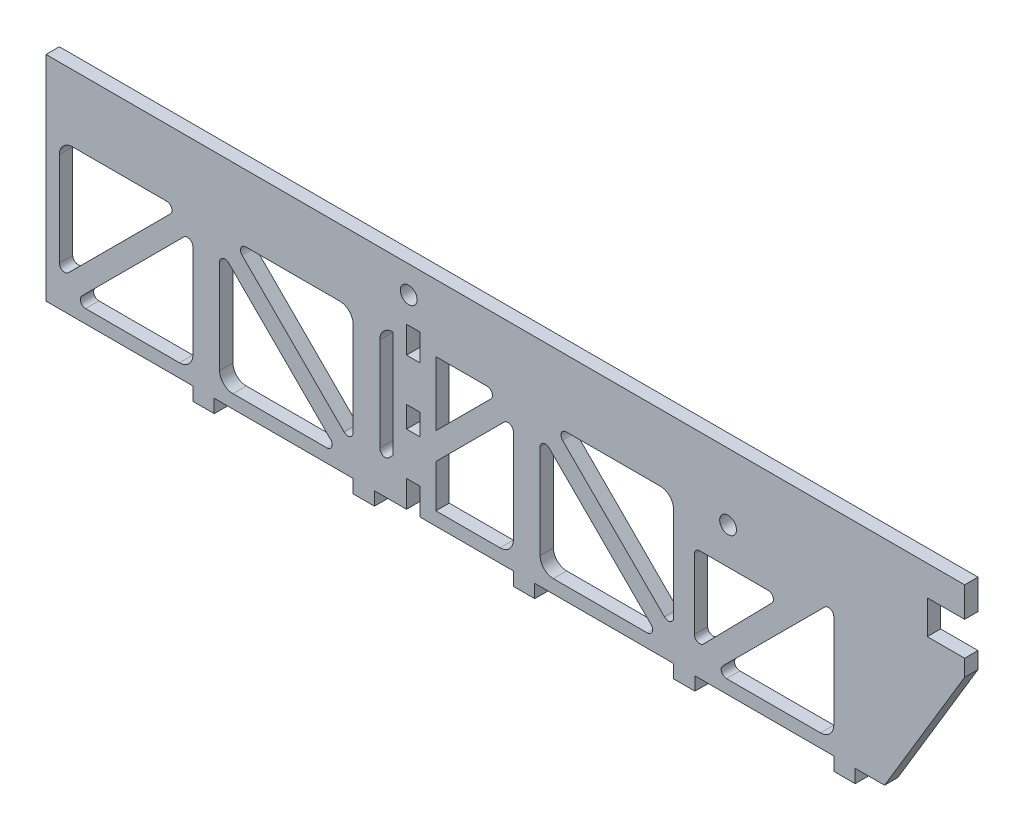
SolidWorks part; units mm, degrees
material "Pine"
ref_plane "Front Plane" through (0, 0, 0) normal (0, 0, 1) x (1, 0, 0)
ref_plane "Top Plane" through (0, 0, 0) normal (0, 1, 0) x (1, 0, 0)
ref_plane "Right Plane" through (0, 0, 0) normal (1, 0, 0) x (0, 0, -1)
sketch "Model" plane through (0, 0, 0) normal (0, 0, 1) x (1, 0, 0)
  line L0 (312.6855, 15.1239) -> (345.2281, 48.2988)
  line L1 (343.4149, 52.6175) -> (310.8722, 52.6175)
  line L2 (308.3322, 50.0775) -> (308.3322, 16.9026)
  line L8 (171.2321, 6.35) -> (215.9, 6.35)
  line L9 (217.9139, 59.1639) -> (169.4361, 10.6861)
  line L10 (222.25, 57.3679) -> (222.25, 12.7)
  line L11 (234.95, 57.3679) -> (234.95, 12.7)
  line L12 (239.2861, 59.1639) -> (287.7639, 10.6861)
  line L13 (241.3, 6.35) -> (285.9679, 6.35)
  line L14 (294.1139, 17.0361) -> (245.6361, 65.5139)
  line L15 (247.4321, 69.85) -> (292.1, 69.85)
  line L16 (298.45, 63.5) -> (298.45, 18.8321)
  line L17 (323.6321, 6.35) -> (368.3, 6.35)
  line L18 (370.3139, 59.1639) -> (321.8361, 10.6861)
  line L19 (374.65, 57.3679) -> (374.65, 12.7)
  line L20 (18.8321, 6.35) -> (63.5, 6.35)
  line L21 (17.0361, 10.6861) -> (65.5139, 59.1639)
  line L22 (69.85, 57.3679) -> (69.85, 12.7)
  line L23 (82.55, 57.3679) -> (82.55, 12.7)
  line L24 (86.8861, 59.1639) -> (135.3639, 10.6861)
  line L25 (88.9, 6.35) -> (133.5679, 6.35)
  line L26 (93.2361, 65.5139) -> (141.7139, 17.0361)
  line L27 (95.0321, 69.85) -> (139.7, 69.85)
  line L28 (146.05, 63.5) -> (146.05, 18.8321)
  line L29 (163.0861, 17.0361) -> (211.5639, 65.5139)
  line L30 (158.75, 63.5) -> (158.75, 18.8321)
  line L31 (165.1, 69.85) -> (209.7679, 69.85)
  line L35 (419.1, 87.376) -> (419.1, 71.374)
  line L36 (436.88, 87.376) -> (419.1, 87.376)
  line L37 (436.88, 87.376) -> (436.88, 95.25)
  line L38 (0, 95.25) -> (436.88, 95.25)
  line L39 (0, 0) -> (0, 95.25)
  line L40 (0, 0) -> (398.78, 0)
  line L41 (436.88, 63.5) -> (398.78, 0)
  line L42 (436.88, 63.5) -> (436.88, 71.374)
  line L43 (419.1, 71.374) -> (436.88, 71.374)
  line L44 (6.35, 63.5) -> (6.35, 18.8321)
  line L45 (12.7, 69.85) -> (57.3679, 69.85)
  line L46 (59.1639, 65.5139) -> (10.6861, 17.0361)
  arc A0 (215.9, 6.35) -> (222.25, 12.7) centre (215.9, 12.7) ccw
  arc A1 (169.4361, 10.6861) -> (171.2321, 6.35) centre (171.2321, 8.89) ccw
  arc A2 (222.25, 57.3679) -> (217.9139, 59.1639) centre (219.71, 57.3679) ccw
  arc A3 (239.2861, 59.1639) -> (234.95, 57.3679) centre (237.49, 57.3679) ccw
  arc A4 (285.9679, 6.35) -> (287.7639, 10.6861) centre (285.9679, 8.89) ccw
  arc A5 (234.95, 12.7) -> (241.3, 6.35) centre (241.3, 12.7) ccw
  arc A6 (247.4321, 69.85) -> (245.6361, 65.5139) centre (247.4321, 67.31) ccw
  arc A7 (298.45, 63.5) -> (292.1, 69.85) centre (292.1, 63.5) ccw
  arc A8 (294.1139, 17.0361) -> (298.45, 18.8321) centre (295.91, 18.8321) ccw
  arc A9 (321.8361, 10.6861) -> (323.6321, 6.35) centre (323.6321, 8.89) ccw
  arc A10 (374.65, 57.3679) -> (370.3139, 59.1639) centre (372.11, 57.3679) ccw
  arc A11 (368.3, 6.35) -> (374.65, 12.7) centre (368.3, 12.7) ccw
  arc A12 (63.5, 6.35) -> (69.85, 12.7) centre (63.5, 12.7) ccw
  arc A13 (17.0361, 10.6861) -> (18.8321, 6.35) centre (18.8321, 8.89) ccw
  arc A14 (69.85, 57.3679) -> (65.5139, 59.1639) centre (67.31, 57.3679) ccw
  arc A15 (86.8861, 59.1639) -> (82.55, 57.3679) centre (85.09, 57.3679) ccw
  arc A16 (133.5679, 6.35) -> (135.3639, 10.6861) centre (133.5679, 8.89) ccw
  arc A17 (82.55, 12.7) -> (88.9, 6.35) centre (88.9, 12.7) ccw
  arc A18 (95.0321, 69.85) -> (93.2361, 65.5139) centre (95.0321, 67.31) ccw
  arc A19 (146.05, 63.5) -> (139.7, 69.85) centre (139.7, 63.5) ccw
  arc A20 (141.7139, 17.0361) -> (146.05, 18.8321) centre (143.51, 18.8321) ccw
  arc A21 (158.75, 18.8321) -> (163.0861, 17.0361) centre (161.29, 18.8321) ccw
  arc A22 (165.1, 69.85) -> (158.75, 63.5) centre (165.1, 63.5) ccw
  arc A23 (211.5639, 65.5139) -> (209.7679, 69.85) centre (209.7679, 67.31) ccw
  arc A24 (345.2281, 48.2988) -> (343.4149, 52.6175) centre (343.4149, 50.0775) ccw
  arc A25 (310.8722, 52.6175) -> (308.3322, 50.0775) centre (310.8722, 50.0775) ccw
  arc A26 (312.6855, 15.1239) -> (308.3322, 16.9026) centre (310.8722, 16.9026) cw
  arc A27 (6.35, 18.8321) -> (10.6861, 17.0361) centre (8.89, 18.8321) ccw
  arc A28 (12.7, 69.85) -> (6.35, 63.5) centre (12.7, 63.5) ccw
  arc A29 (59.1639, 65.5139) -> (57.3679, 69.85) centre (57.3679, 67.31) ccw
  circle A30 centre (172.4917, 88.8013) radius 4
  circle A31 centre (324.3837, 70.0053) radius 4
  dimension "D2" = 6.4487
  dimension "D3" = 172.4917
  dimension "D4" = 8
  dimension "D5" = 18.796
  dimension "D6" = 8
  dimension "D8" = 2.54
  dimension "D1" = 95.25
  dimension "D7" = 151.892
extrude "Boss-Extrude2" add sketch "Model" along normal blind 6.35
sketch "Sketch1" plane through (0, 0, 6.35) normal (0, 0, 1) x (1, 0, 0)
  line L0 (69.85, 12.7) -> (69.85, 0) construction
  line L1 (146.05, 95.25) -> (146.05, 0) construction
  line L2 (146.05, 18.8321) -> (146.05, 63.5) construction
  line L3 (0, 0) -> (398.78, 0) construction
  line L4 (222.25, 95.25) -> (222.25, 0) construction
  line L5 (222.25, 12.7) -> (222.25, 57.3679) construction
  line L6 (298.45, 18.8321) -> (298.45, 0) construction
  line L7 (146.05, 0) -> (156.21, 0)
  line L8 (69.85, 0) -> (80.01, 0)
  line L9 (69.85, 0) -> (69.85, -6.35)
  line L10 (69.85, -6.35) -> (80.01, -6.35)
  line L11 (80.01, 0) -> (80.01, -6.35)
  line L16 (222.25, 0) -> (232.41, 0)
  line L17 (222.25, 0) -> (222.25, -6.35)
  line L18 (222.25, -6.35) -> (232.41, -6.35)
  line L19 (232.41, 0) -> (232.41, -6.35)
  line L20 (146.05, 0) -> (146.05, -6.35)
  line L21 (146.05, -6.35) -> (156.21, -6.35)
  line L22 (156.21, 0) -> (156.21, -6.35)
  line L24 (374.65, 12.7) -> (374.65, 0) construction
  line L25 (374.65, 12.7) -> (374.65, 57.3679) construction
  line L27 (298.45, 0) -> (308.61, 0)
  line L28 (298.45, 0) -> (298.45, -6.35)
  line L29 (298.45, -6.35) -> (308.61, -6.35)
  line L30 (308.61, 0) -> (308.61, -6.35)
  line L31 (374.65, 0) -> (384.81, 0)
  line L32 (374.65, 0) -> (374.65, -6.35)
  line L33 (374.65, -6.35) -> (384.81, -6.35)
  line L34 (384.81, 0) -> (384.81, -6.35)
  line L39 (0, 101.6) -> (436.88, 101.6)
  line L53 (0, 95.25) -> (0, 101.6)
  line L55 (436.88, 95.25) -> (436.88, 101.6)
  line L56 (436.88, 95.25) -> (0, 95.25) construction
  line L57 (0, 95.25) -> (436.88, 95.25)
  arc A0 (368.3, 6.35) -> (374.65, 12.7) centre (368.3, 12.7) ccw construction
  dimension "D1" = 10.16
  dimension "D2" = 6.35
  dimension "D3" = 10.16
  dimension "D4" = 6.35
  dimension "D5" = 10.16
  dimension "D6" = 10.16
  dimension "D7" = 10.16
  dimension "D13" = 6.35
extrude "Boss-Extrude3" add sketch "Sketch1" against normal up to surface (6.35 mm away) up to face at (321.5295, 39.2174, 0)
sketch "Sketch2" plane through (0, 0, 6.35) normal (0, 0, 1) x (1, 0, 0)
  line L0 (156.21, 0) -> (222.25, 0) construction
  line L1 (165.1, 79.7539) -> (185.42, 79.7539)
  line L2 (165.1, 79.7539) -> (165.1, 0)
  line L3 (165.1, 0) -> (185.42, 0)
  line L4 (185.42, 79.7539) -> (185.42, 0)
  line L5 (158.75, 63.5) -> (158.75, 18.8321) construction
  line L7 (171.45, 0) -> (177.8, 0)
  line L8 (171.45, 0) -> (171.45, 12.7)
  line L9 (171.45, 12.7) -> (177.8, 12.7)
  line L10 (177.8, 0) -> (177.8, 12.7)
  line L11 (171.45, 33.02) -> (177.8, 33.02)
  line L12 (171.45, 33.02) -> (171.45, 43.18)
  line L13 (171.45, 43.18) -> (177.8, 43.18)
  line L14 (177.8, 33.02) -> (177.8, 43.18)
  line L15 (171.45, 63.5) -> (177.8, 63.5)
  line L16 (171.45, 63.5) -> (171.45, 76.2)
  line L17 (171.45, 76.2) -> (177.8, 76.2)
  line L18 (177.8, 63.5) -> (177.8, 76.2)
  line L19 (146.05, -6.35) -> (156.21, -6.35) construction
  point P20 (177.8, 33.02)
  point P21 (177.8, 43.18)
  dimension "D1" = 6.35
  dimension "D2" = 20.32
  dimension "D3" = 6.35
  dimension "D4" = 6.35
  dimension "D5" = 6.35
  dimension "D6" = 12.7
  dimension "D7" = 20.32
  dimension "D8" = 20.32
  dimension "D9" = 10.16
  dimension "D10" = 12.7
extrude "Boss-Extrude4" add sketch "Sketch2" against normal up to surface (6.35 mm away) contours L10 L3 L4 L1 L2 L8 L9 L18 L15 L16 L17 L14 L11 L12 L13 region at (175.26, 78.9309, 6.35) up to face at (321.5295, 39.2174, 0)
extrude "Cut-Extrude1" cut sketch "Sketch2<3>" along direction (0, 0, 1) on the side against the normal up to surface (6.35 mm away) from surface contours L3 L10 L9 L8 | L15 L18 L17 L16 region at (174.625, 6.35, 6.35) region at (174.625, 69.85, 6.35) up to face at (174.625, 9.525, 0) starting at face at (174.625, 9.525, 6.35)
sketch "Sketch2<3>" plane through (0, 0, 6.35) normal (0, 0, 1) x (1, 0, 0) same geometry as "Sketch2"
